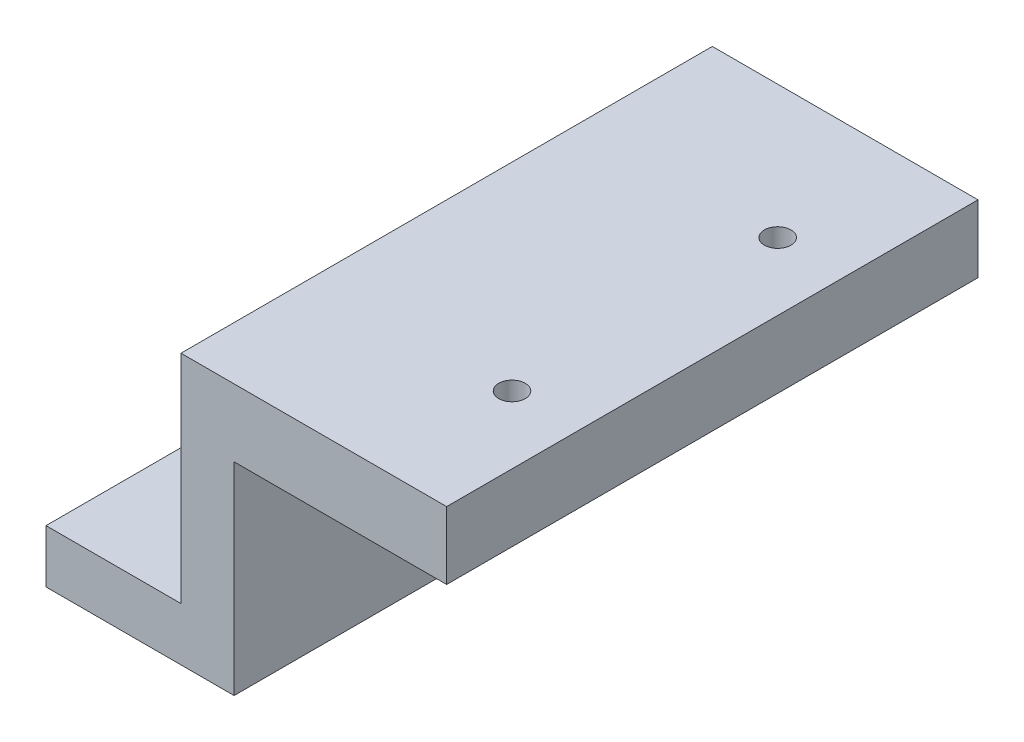
SolidWorks part; units mm, degrees
material "ABS"
ref_plane "Front Plane" through (0, 0, 0) normal (0, 0, 1) x (1, 0, 0)
ref_plane "Top Plane" through (0, 0, 0) normal (0, 1, 0) x (1, 0, 0)
ref_plane "Right Plane" through (0, 0, 0) normal (1, 0, 0) x (0, 0, -1)
sketch "Sketch1" plane through (0, 0, 0) normal (0, 0, 1) x (1, 0, 0)
  line L1 (-25, -6.35) -> (25, -6.35)
  line L2 (-25, -6.35) -> (-25, 6.35)
  line L3 (-25, 6.35) -> (25, 6.35)
  line L4 (25, -6.35) -> (25, 6.35)
  line L5 (-25, -6.35) -> (25, 6.35) construction
  line L6 (-25, 6.35) -> (25, -6.35) construction
  point P0 (0, 0)
  dimension "D1" = 12.7
  dimension "D2" = 50
extrude "Boss-Extrude1" add sketch "Sketch1" along normal blind 100
sketch "Sketch2" plane through (0, -6.35, 0) normal (0, -1, 0) x (1, 0, 0)
  line L0 (-25, 0) -> (25, 0) construction
  line L1 (-25, 100) -> (-15, 100)
  line L2 (-25, 100) -> (-25, 0)
  line L3 (-25, 0) -> (-15, 0)
  line L4 (-15, 100) -> (-15, 0)
  dimension "D1" = 10
extrude "Boss-Extrude2" add sketch "Sketch2" along normal blind 38.1
sketch "Sketch3" plane through (-25, 0, 0) normal (-1, 0, 0) x (0, 0, 1)
  line L0 (100, 6.35) -> (100, -44.45) construction
  line L1 (0, -44.45) -> (100, -44.45)
  line L2 (0, -44.45) -> (0, -34.45)
  line L3 (0, -34.45) -> (100, -34.45)
  line L4 (100, -44.45) -> (100, -34.45)
  dimension "D1" = 10
extrude "Boss-Extrude3" add sketch "Sketch3" along normal blind 25.4
sketch "Sketch4" plane through (0, 6.35, 0) normal (0, 1, 0) x (1, 0, 0)
  line L0 (25, -100) -> (-25, -100) construction
  line L1 (25, 0) -> (-0.4, 0)
  line L2 (25, 0) -> (25, -100)
  line L3 (25, -100) -> (-0.4, -100)
  line L4 (-0.4, 0) -> (-0.4, -100)
  line L5 (-0.4, -100) -> (25, 0) construction
  line L6 (12.3, -50) -> (12.3, 0) construction
  line L7 (12.3, -50) -> (12.3, -100) construction
  point P9 (12.3, -25)
  point P11 (12.3, -75)
  point P13 (12.3, -25)
  point P15 (12.3, -75)
  dimension "D1" = 25.4
sketch "Sketch7" plane through (-15, 0, 0) normal (1, 0, 0) x (0, 0, -1)
  line L0 (-100, -44.45) -> (-100, -6.35) construction
  line L1 (0, -6.35) -> (-100, -6.35)
  line L2 (0, -6.35) -> (0, -44.45)
  line L3 (0, -44.45) -> (-100, -44.45)
  line L4 (-100, -6.35) -> (-100, -44.45)
  line L8 (-50, -6.35) -> (-50, -44.45) construction
  line L11 (0, -44.45) -> (-100, -44.45) construction
  point P28 (-73, -27.45)
  point P31 (-27, -27.45)
  point P35 (-73, -9.45)
  point P37 (-27, -9.45)
  dimension "D3" = 35
  dimension "D2" = 46
  dimension "D1" = 18
hole_wizard "M5x0.8 Tapped Hole1" positions "Sketch4" profile "Sketch8" tap size "M5x0.8" standard "ANSI Metric" end condition through all
sketch "Sketch8" plane through (12.3, 6.35, 75) normal (1, 0, 0) x (0, 0, 1)
  line L0 (0, 0) -> (0, 50.8)
  line L1 (0, 50.8) -> (2.5, 50.8)
  line L2 (2.5, 50.8) -> (2.5, 0)
  line L5 (2.5, 0) -> (0, 0)
  line L11 (0, -6.35) -> (0, 107.95) construction
  dimension "Thread Major Dia." = 5
  dimension "Thru Tap Drill Depth" = 50.8
hole_wizard "M5x0.8 Tapped Hole2" positions "Sketch7" profile "Sketch9" tap size "M5x0.8" standard "ANSI Metric" end condition through all
sketch "Sketch9" plane through (-15, -9.45, 27) normal (0, 1, 0) x (0, 0, -1)
  line L0 (0, 0) -> (0, 35.4)
  line L1 (0, 35.4) -> (2.5, 35.4)
  line L2 (2.5, 35.4) -> (2.5, 0)
  line L5 (2.5, 0) -> (0, 0)
  line L11 (0, -6.35) -> (0, 107.95) construction
  dimension "Thread Major Dia." = 5
  dimension "Thru Tap Drill Depth" = 35.4
